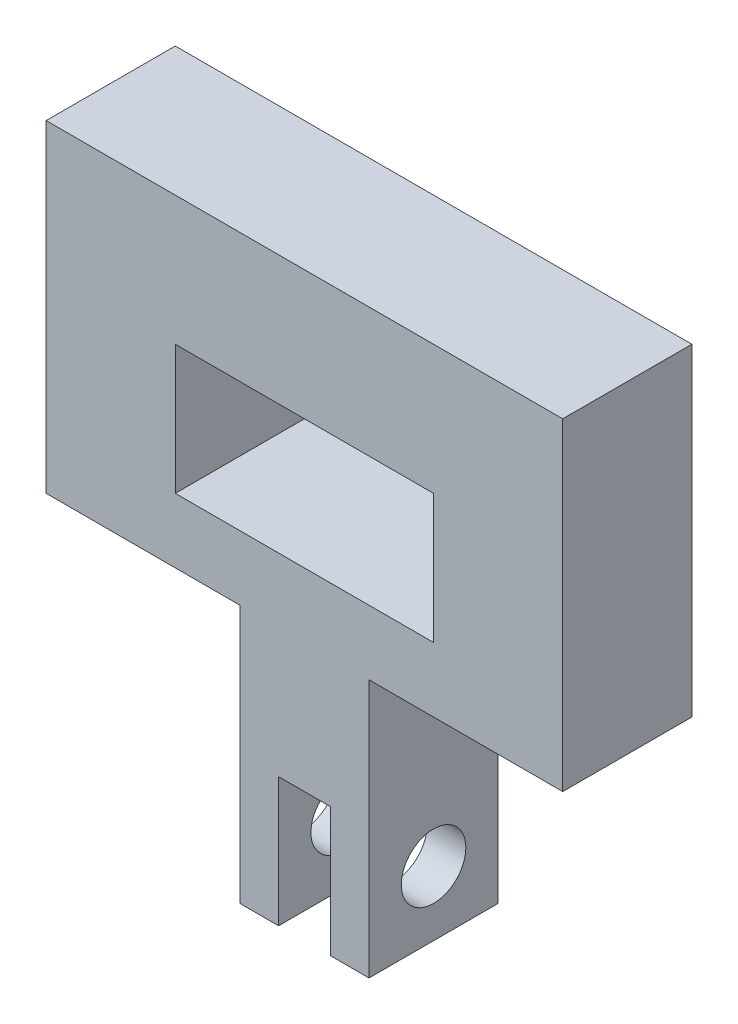
SolidWorks part; units mm, degrees
ref_plane "Plan de face" through (0, 0, 0) normal (0, 0, 1) x (1, 0, 0)
ref_plane "Plan de dessus" through (0, 0, 0) normal (0, 1, 0) x (1, 0, 0)
ref_plane "Plan de droite" through (0, 0, 0) normal (1, 0, 0) x (0, 0, -1)
sketch "Esquisse1" plane through (0, 0, 0) normal (0, 0, 1) x (1, 0, 0)
  line L0 (0, 25.1724) -> (0, -64.1379) construction
  line L1 (-10, 5) -> (10, 5)
  line L2 (-10, 5) -> (-10, -5)
  line L3 (-10, -5) -> (10, -5)
  line L4 (10, 5) -> (10, -5)
  line L5 (-10, 5) -> (10, -5) construction
  line L6 (-10, -5) -> (10, 5) construction
  line L7 (-20, 15) -> (20, 15)
  line L8 (-20, 15) -> (-20, -10)
  line L10 (20, 15) -> (20, -10)
  line L11 (-20, -10) -> (-5, -10)
  line L12 (-5, -10) -> (-5, -30)
  line L13 (-5, -30) -> (-2, -30)
  line L14 (5, -30) -> (5, -10)
  line L15 (5, -10) -> (20, -10)
  line L16 (-2, -30) -> (-2, -20)
  line L17 (-2, -20) -> (2, -20)
  line L18 (2, -20) -> (2, -30)
  line L19 (2, -30) -> (5, -30)
  point P0 (0, 0)
  point P7 (0, 0)
  dimension "D7" = 10
  dimension "D1" = 20
  dimension "D2" = 10
  dimension "D3" = 10
  dimension "D4" = 10
  dimension "D5" = 10
  dimension "D6" = 25
  dimension "D8" = 15
  dimension "D9" = 15
  dimension "D10" = 20
  dimension "D11" = 3
  dimension "D12" = 3
  dimension "D13" = 10
extrude "Boss.-Extru.1" add sketch "Esquisse1" along normal blind 5 and the other way blind 5
sketch "Esquisse3" plane through (5, 0, 0) normal (1, 0, 0) x (0, 0, -1)
  line L0 (5, -30) -> (-5, -30) construction
  circle A0 centre (0, -25) radius 2.5
  dimension "D1" = 5
  dimension "D2" = 5
extrude "Enlèv. mat.-Extru.1" cut sketch "Esquisse3" against normal through all
